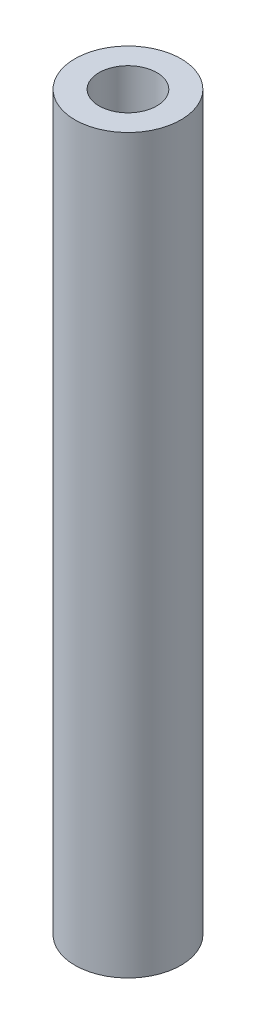
SolidWorks part; units mm, degrees
material "1060 Alloy"
ref_plane "Front" through (0, 0, 0) normal (0, 0, 1) x (1, 0, 0)
ref_plane "Top" through (0, 0, 0) normal (0, 1, 0) x (1, 0, 0)
ref_plane "Right" through (0, 0, 0) normal (1, 0, 0) x (0, 0, -1)
sketch "Sketch1" plane through (0, 0, 0) normal (0, 1, 0) x (1, 0, 0)
  circle A0 centre (0, 0) radius 2.75
  circle A1 centre (0, 0) radius 1.5
  dimension "D1" = 5.5
  dimension "D2" = 3
extrude "Boss-Extrude1" add sketch "Sketch1" along normal blind 38
